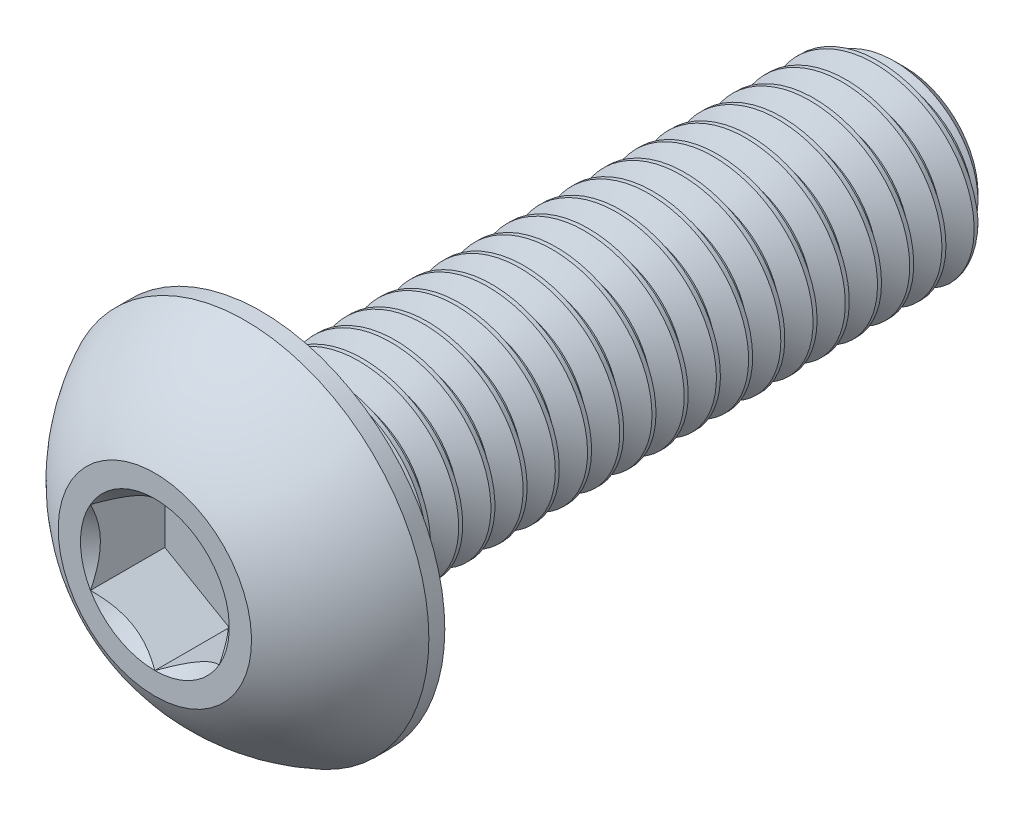
SolidWorks part; units mm, degrees
ref_plane "Front" through (0, 0, 0) normal (0, 0, 1) x (1, 0, 0)
ref_plane "Top" through (0, 0, 0) normal (0, 1, 0) x (1, 0, 0)
ref_plane "Right" through (0, 0, 0) normal (1, 0, 0) x (0, 0, -1)
sketch "Sketch1" plane through (0, 0, 0) normal (1, 0, 0) x (0, 0, -1)
  line L2 (1.65, 1.5) -> (11.65, 1.5)
  line L3 (11.65, 1.5) -> (11.65, 0)
  line L4 (11.65, 0) -> (1.65, 0)
  line L6 (1.4025, 2.85) -> (1.65, 2.85) construction
  line L7 (11.65, 1.5) -> (11.65, -1.5) construction
  line L8 (0, 0) -> (1.65, 0) construction
  line L9 (1.65, 2.85) -> (1.65, -2.85) construction
  line L11 (1.65, 1.5) -> (1.65, 0)
  line L13 (0, 1) -> (0, -1) construction
  line L14 (0, 1) -> (0, 1.5) construction
  arc A3 (0, 1.5) -> (1.4025, 2.85) centre (2.7948, 0) cw construction
  dimension "D1" = 0.2475
revolve "Revolve1" add sketch "Sketch1" angle 360 mid plane about L4
sketch "Sketch3" plane through (0, 0, -11.65) normal (0, 0, -1) x (-1, 0, 0)
  circle A0 centre (0, 0) radius 1.5
curve "Helix/Spiral1" pitch 0.5 height 10.5 radius 1.5 centre (0, 0, -11.65) axis (0, 0, 1) start towards (0, 1, 0)
sketch "Sketch2" plane through (0, 0, 0) normal (1, 0, 0) x (0, 0, -1)
  line L0 (11.65, 1.5) -> (12.0875, 1.5)
  line L1 (12.0875, 1.5) -> (11.9, 1.1752)
  line L2 (11.9, 1.1752) -> (11.8375, 1.1752)
  line L3 (11.8375, 1.1752) -> (11.65, 1.5)
  line L4 (11.7438, 1.3376) -> (11.9938, 1.3376) construction
  dimension "D1" = 60
  dimension "D2" = 0.0625
  dimension "D3" = 0.25
chamfer "Chamfer1" distance 0.375 angle 45 1 edges at (0, 1.5, -11.65)
sweep "Cut-Sweep1" cut profiles "Sketch2" path "Helix/Spiral1" align with end faces yes
sketch "Sketch7" plane through (0, 0, 0) normal (1, 0, 0) x (0, 0, -1)
  line L6 (1.4025, 2.85) -> (1.65, 2.85) construction
  line L8 (0, 0) -> (1.65, 0) construction
  line L11 (1.65, 2.85) -> (1.65, -2.85) construction
  line L12 (1.4025, 2.85) -> (1.65, 2.85)
  line L13 (0, 0) -> (1.65, 0)
  line L14 (0, 1) -> (0, -1) construction
  line L15 (1.65, 2.85) -> (1.65, 0)
  line L16 (0, 1.5) -> (0, 0)
  arc A2 (1.4025, 2.85) -> (0, 1.5) centre (2.7948, 0) ccw construction
  arc A3 (1.4025, 2.85) -> (0, 1.5) centre (2.7948, 0) ccw
revolve "Revolve2" add sketch "Sketch7" angle 360 mid plane about L13
sketch "Sketch5" plane through (0, 0, 0) normal (0, 0, 1) x (1, 0, 0)
  line L1 (1, -0.5774) -> (1, 0.5774)
  line L2 (1, 0.5774) -> (0, 1.1547)
  line L3 (0, 1.1547) -> (-1, 0.5774)
  line L4 (-1, 0.5774) -> (-1, -0.5774)
  line L5 (-1, -0.5774) -> (0, -1.1547)
  line L6 (0, -1.1547) -> (1, -0.5774)
  circle A0 centre (0, 0) radius 1 construction
extrude "Cut-Extrude2" cut sketch "Sketch5" against normal blind 1.155
sketch "Sketch6" plane through (0, 0, 0) normal (0, 0, 1) x (1, 0, 0)
  circle A0 centre (0, 0) radius 1.1547
extrude "Cut-Extrude3" cut sketch "Sketch6" against normal blind 1.155 draft 45
sketch "Sketch9" [suppressed] plane through (0, 0, -4.2164) normal (0, 0, 1) x (1, 0, 0)
  circle A2 centre (0, 0) radius 3.9687
extrude "Boss-Extrude2" [suppressed] add sketch "Sketch9" against normal offset from surface (9.525 mm away) 28.575 up to face at (0, 1.125, -11.65)
sketch "Sketch10" plane through (0, 0, 0) normal (1, 0, 0) x (0, 0, -1)
  line L0 (11.65, 1.5) -> (11.65, -1.5) construction
  point P0 (10.9, -1.5)
  dimension "D1" = 0.75
equation "\"D3@Helix/Spiral1\" = \"Lg@Sketch1\" + \"D4@Helix/Spiral1\""
equation "\"D2@Sketch2\" = \"D4@Helix/Spiral1\" * .125"
equation "\"D3@Sketch2\" = \"D4@Helix/Spiral1\" * .5"
equation "\"D1@Chamfer1\" = \"D4@Helix/Spiral1\" * .75"
equation "\"D1@Cut-Extrude2\" = \"Head Ht@Sketch1\" * .7"
equation "\"D1@Sketch1\" = \"Head Ht@Sketch1\" * .15"
equation "\"D1@Sketch10\" = \"D4@Helix/Spiral1\" * 1.5"
equation "\"D1@Cut-Extrude3\" = \"D1@Cut-Extrude2\""
